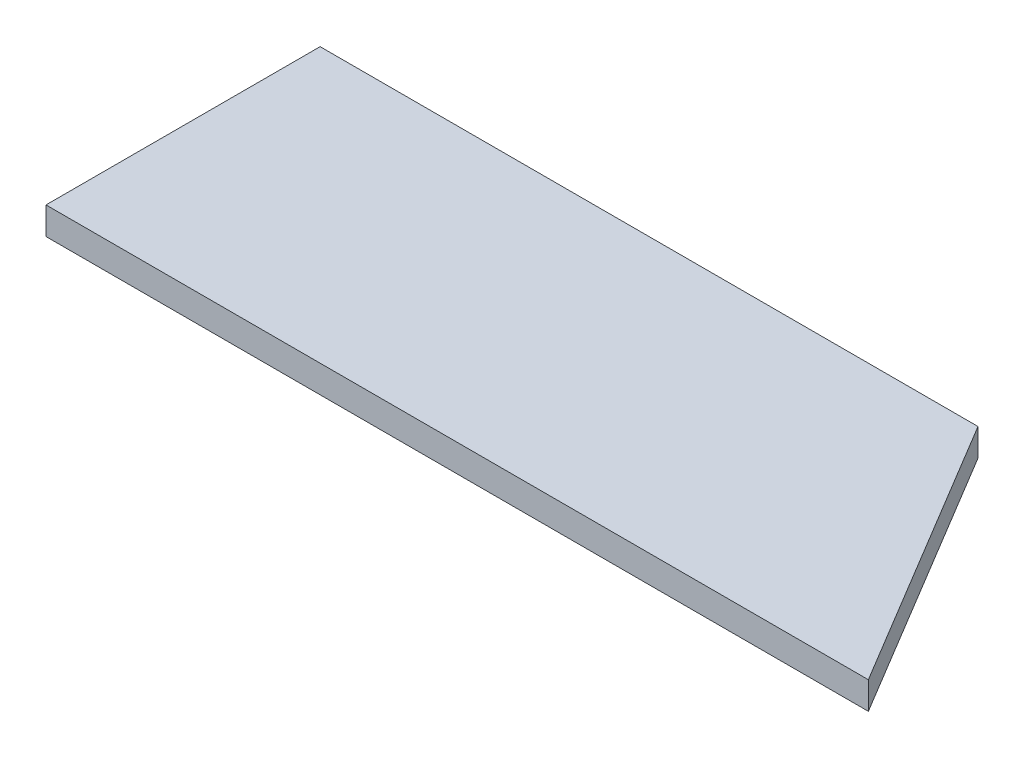
SolidWorks part; units mm, degrees
ref_plane "Спереди" through (0, 0, 0) normal (0, 0, 1) x (1, 0, 0)
ref_plane "Сверху" through (0, 0, 0) normal (0, 1, 0) x (1, 0, 0)
ref_plane "Справа" through (0, 0, 0) normal (1, 0, 0) x (0, 0, -1)
sketch "Эскиз1" plane through (0, 0, 0) normal (0, 1, 0) x (1, 0, 0)
  line L0 (0, 0) -> (150, 0)
  line L1 (150, 0) -> (120, 50)
  line L2 (120, 50) -> (0, 50)
  line L3 (0, 50) -> (0, 0)
extrude "Бобышка-Вытянуть1" add sketch "Эскиз1" along normal blind 5
